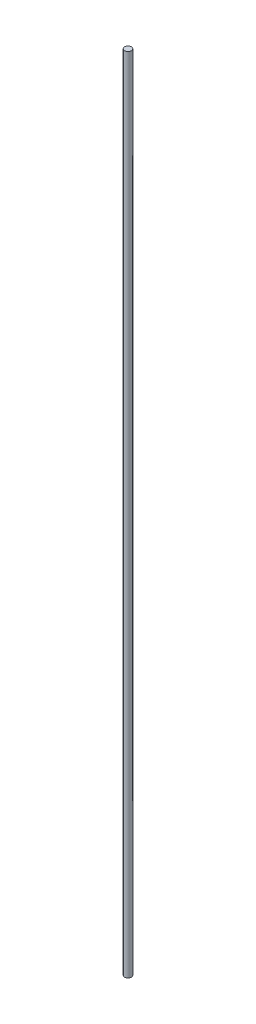
SolidWorks part; units mm, degrees
material "6061-T6 (SS)"
ref_plane "Front Plane" through (0, 0, 0) normal (1, 0, 0) x (0, 1, 0)
ref_plane "Top Plane" through (0, 0, 0) normal (0, 0, 1) x (0, 1, 0)
ref_plane "Right Plane" through (0, 0, 0) normal (0, 1, 0) x (-1, 0, 0)
sketch "Sketch1" plane through (0, 0, 0) normal (0, 1, 0) x (-1, 0, 0)
  circle A0 centre (0, 0) radius 6.35
  dimension "D1" = 12.7
extrude "Boss-Extrude1" add sketch "Sketch1" along normal blind 1497.33
ref_axis "Axis1" through (0, 1497.33, 0) along (0, -1, 0)
equation "\"Modulus\"= 10007604"
equation "\"F\"= 300"
equation "\"diameter\" = 0.5in"
equation "\"area\"= ( pi / 4 ) * ( \"diameter\" ^ 2 )"
equation "\"maddef\"= 0.009in"
equation "\"length\"= \"Modulus\" * ( 1 / \"F\" ) * \"area\" * \"maddef\""
equation "\"D1@Sketch1\" = \"diameter\""
